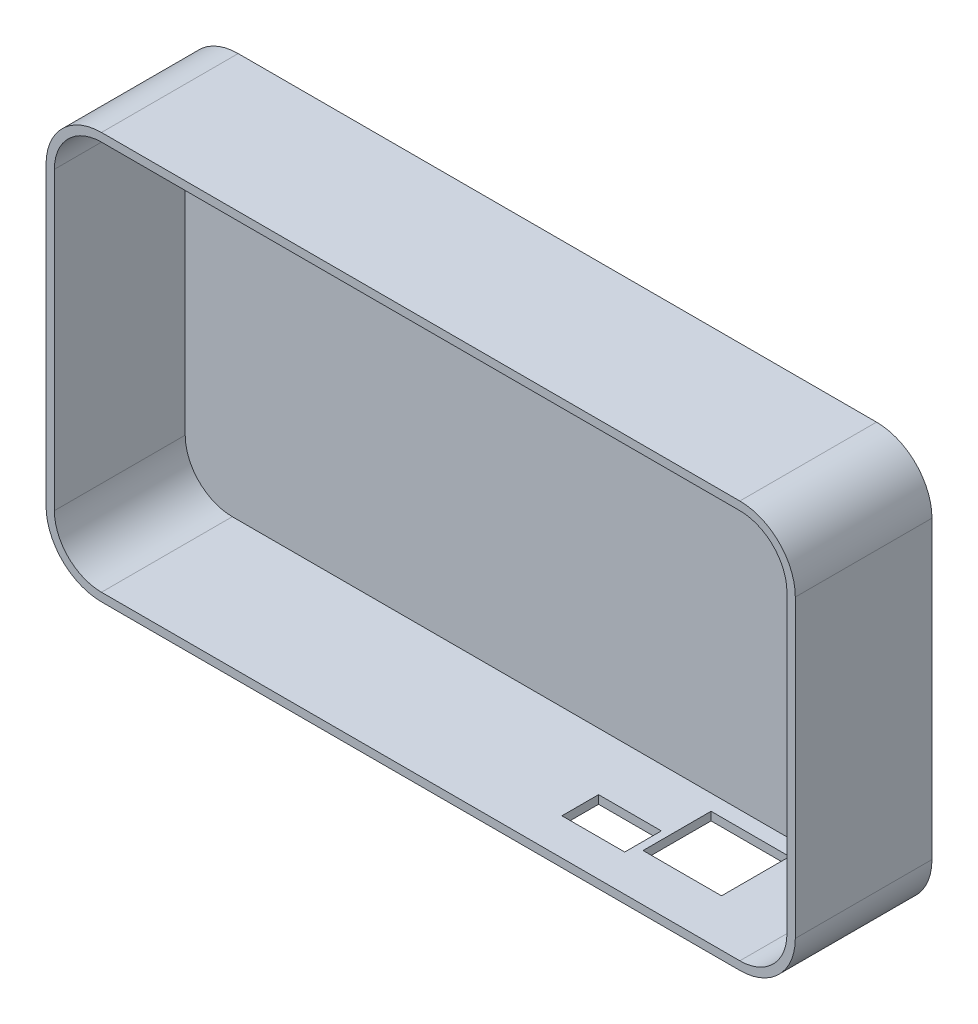
SolidWorks part; units mm, degrees
ref_plane "Alzado" through (0, 0, 0) normal (0, 0, 1) x (1, 0, 0)
ref_plane "Planta" through (0, 0, 0) normal (0, 1, 0) x (1, 0, 0)
ref_plane "Vista lateral" through (0, 0, 0) normal (1, 0, 0) x (0, 0, -1)
sketch "Croquis1" plane through (0, 0, 0) normal (0, 0, 1) x (1, 0, 0)
  line L0 (9, 76.1) -> (131, 76.1)
  line L1 (9, 0) -> (131, 0)
  line L2 (0, 9) -> (0, 65.5)
  line L3 (9, 74.5) -> (131, 74.5)
  line L4 (140, 9) -> (140, 65.5)
  line L5 (141.6, 9) -> (141.6, 65.5)
  line L6 (9, -1.6) -> (131, -1.6)
  line L7 (-1.6, 9) -> (-1.6, 65.5)
  arc A0 (131, 74.5) -> (140, 65.5) centre (131, 65.5) cw
  arc A1 (131, 0) -> (140, 9) centre (131, 9) ccw
  arc A2 (9, 0) -> (0, 9) centre (9, 9) cw
  arc A3 (0, 65.5) -> (9, 74.5) centre (9, 65.5) cw
  arc A4 (131, 76.1) -> (141.6, 65.5) centre (131, 65.5) cw
  arc A5 (131, -1.6) -> (141.6, 9) centre (131, 9) ccw
  arc A6 (9, -1.6) -> (-1.6, 9) centre (9, 9) cw
  arc A7 (-1.6, 65.5) -> (9, 76.1) centre (9, 65.5) cw
  point P9 (140, 0)
  point P12 (0, 0)
  point P15 (0, 74.5)
  dimension "D3" = 9
  dimension "D1" = 140
  dimension "D2" = 74.5
  dimension "D4" = 1.6
extrude "pared" add sketch "Croquis1" along normal blind 25
sketch "Croquis2" plane through (0, -1.6, 0) normal (0, -1, 0) x (1, 0, 0)
  line L0 (0, 25) -> (0, 0) construction
  line L1 (140, 25) -> (140, 0) construction
  line L2 (9, 25) -> (-1.6, 25) construction
  line L3 (-1.6, 25) -> (-1.6, 0) construction
  line L4 (-1.6, 0) -> (9, 0) construction
  line L5 (9, 0) -> (131, 0) construction
  line L6 (131, 0) -> (141.6, 0) construction
  line L7 (141.6, 25) -> (141.6, 0) construction
  line L8 (141.6, 25) -> (131, 25) construction
  line L9 (9, 25) -> (131, 25) construction
  line L10 (0, 25) -> (0, 0)
  line L11 (140, 25) -> (140, 0)
  line L12 (9, 25) -> (-1.6, 25)
  line L13 (-1.6, 25) -> (-1.6, 0)
  line L14 (-1.6, 0) -> (9, 0)
  line L15 (9, 0) -> (131, 0)
  line L16 (131, 0) -> (141.6, 0)
  line L17 (141.6, 25) -> (141.6, 0)
  line L18 (141.6, 25) -> (131, 25)
  line L19 (9, 25) -> (131, 25)
  line L21 (103.5, 16) -> (118.5, 16)
  line L22 (103.5, 16) -> (103.5, 3)
  line L23 (103.5, 3) -> (118.5, 3)
  line L24 (118.5, 16) -> (118.5, 3)
  line L25 (90, 18) -> (102, 18)
  line L26 (90, 18) -> (90, 11)
  line L27 (90, 11) -> (102, 11)
  line L28 (102, 18) -> (102, 11)
  dimension "D1" = 3
  dimension "D2" = 13
  dimension "D3" = 21.5
  dimension "D4" = 15
  dimension "D5" = 12
  dimension "D6" = 7
  dimension "D7" = 50
  dimension "D8" = 11
extrude "conectores" cut sketch "Croquis2" against normal up to next contours L24 L21 L22 L23 | L28 L25 L26 L27 region at (111, -1.6, 9.5) region at (96, -1.6, 14.5)
extrude "base frente" add sketch "Croquis1<2>" against normal blind 1.12 contours A6 L7 A7 L0 A4 L5 A5 L6
sketch "Croquis1<2>" plane through (0, 0, 0) normal (0, 0, 1) x (1, 0, 0) same geometry as "Croquis1"
sketch "Croquis3" plane through (0, 0, 0) normal (0, 0, 1) x (1, 0, 0)
  line L0 (131, 35.5) -> (133, 35.5)
  line L1 (131.5, 54) -> (132.5, 54)
  line L2 (131, 53.5) -> (131, 29.5)
  line L3 (131.5, 29) -> (132.5, 29)
  line L4 (140, 9) -> (140, 65.5)
  line L5 (131, 74.5) -> (9, 74.5)
  line L6 (0, 65.5) -> (0, 9)
  line L7 (9, 0) -> (131, 0)
  line L8 (140, 9) -> (140, 65.5)
  line L9 (131, 74.5) -> (9, 74.5)
  line L10 (0, 65.5) -> (0, 9)
  line L11 (9, 0) -> (131, 0)
  line L12 (133, 53.5) -> (133, 29.5)
  line L13 (131.5, 28) -> (132.5, 28)
  line L14 (131, 27.5) -> (131, 13.5)
  line L15 (131.5, 13) -> (132.5, 13)
  line L16 (133, 27.5) -> (133, 13.5)
  line L17 (131, 34.5) -> (133, 34.5)
  line L18 (131, 42) -> (133, 42)
  line L19 (131, 41) -> (133, 41)
  line L20 (131, 48.5) -> (133, 48.5)
  line L21 (131, 47.5) -> (133, 47.5)
  line L22 (131, 41.5) -> (133, 41.5) construction
  line L23 (131, 35.5) -> (131, 42) construction
  arc A0 (131.5, 54) -> (131, 53.5) centre (131.5, 53.5) ccw
  arc A1 (132.5, 54) -> (133, 53.5) centre (132.5, 53.5) cw
  arc A2 (131, 29.5) -> (131.5, 29) centre (131.5, 29.5) ccw
  arc A3 (132.5, 29) -> (133, 29.5) centre (132.5, 29.5) ccw
  arc A4 (131, 0) -> (140, 9) centre (131, 9) ccw
  arc A5 (140, 65.5) -> (131, 74.5) centre (131, 65.5) ccw
  arc A6 (9, 74.5) -> (0, 65.5) centre (9, 65.5) ccw
  arc A7 (0, 9) -> (9, 0) centre (9, 9) ccw
  arc A8 (131, 0) -> (140, 9) centre (131, 9) ccw
  arc A9 (140, 65.5) -> (131, 74.5) centre (131, 65.5) ccw
  arc A10 (9, 74.5) -> (0, 65.5) centre (9, 65.5) ccw
  arc A11 (0, 9) -> (9, 0) centre (9, 9) ccw
  arc A12 (131.5, 28) -> (131, 27.5) centre (131.5, 27.5) ccw
  arc A13 (132.5, 28) -> (133, 27.5) centre (132.5, 27.5) cw
  arc A14 (131, 13.5) -> (131.5, 13) centre (131.5, 13.5) ccw
  arc A15 (132.5, 13) -> (133, 13.5) centre (132.5, 13.5) ccw
  point P32 (133, 28)
  point P37 (133, 13)
  dimension "D8" = 0.5
  dimension "D2" = 2
  dimension "D3" = 7
  dimension "D4" = 25
  dimension "D5" = 29
  dimension "D6" = 1
  dimension "D7" = 15
  dimension "D11" = 6.5
  dimension "D1" = 0
  dimension "D9" = 1
  dimension "D10" = 3
extrude "Cortar-Extruir2" cut sketch "Croquis3" against normal up to next contours L15 A15 L16 A13 L13 A12 L14 A14 | L3 A3 L12 L17 L2 A2 | L19 L2 L0 L12 | L21 L2 L18 L12 | A1 L1 A0 L2 L20 L12 region at (132, 38.25, 0) region at (132, 31.776, 0) region at (132, 44.75, 0) region at (132, 51.224, 0) region at (132, 20.5, 0)
